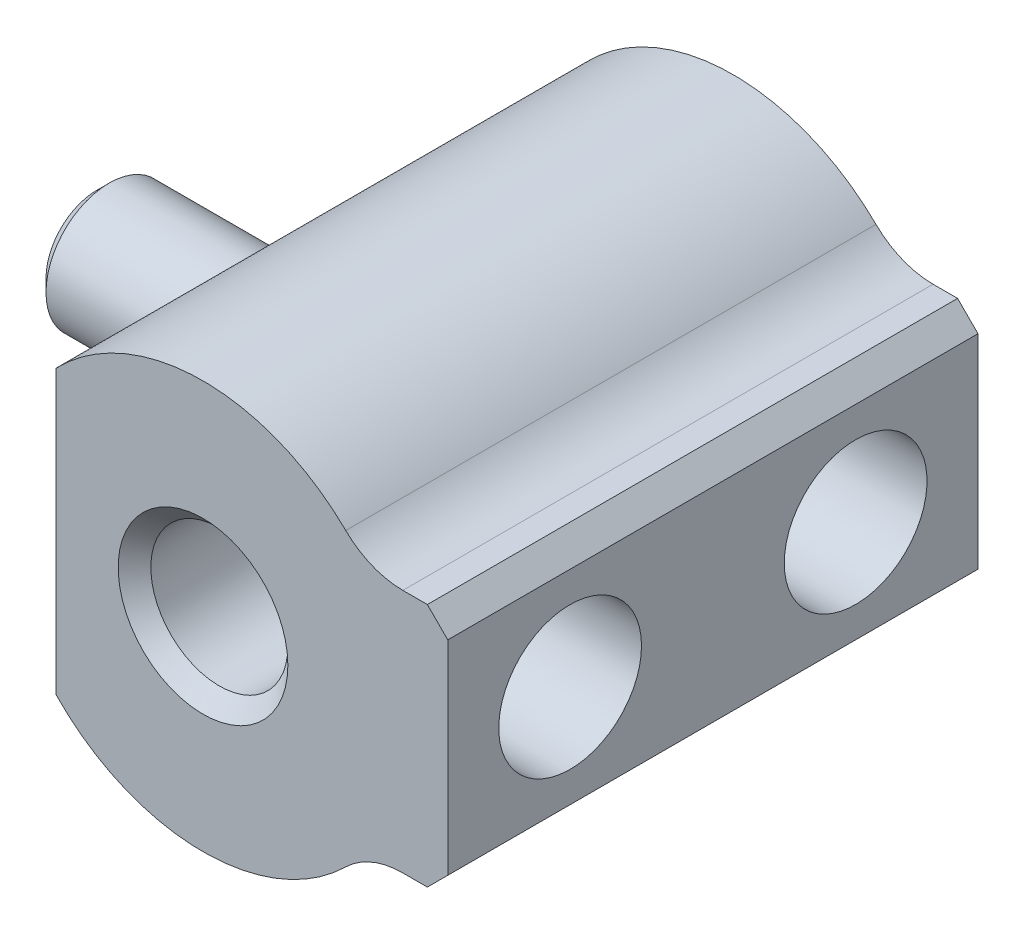
SolidWorks part; units mm, degrees
material "PLA2"
ref_plane "Front Plane" through (0, 0, 0) normal (0, 0, 1) x (1, 0, 0)
ref_plane "Top Plane" through (0, 0, 0) normal (0, 1, 0) x (1, 0, 0)
ref_plane "Right Plane" through (0, 0, 0) normal (1, 0, 0) x (0, 0, -1)
sketch "Sketch1" plane through (0, 0, 0) normal (0, 0, 1) x (1, 0, 0)
  circle A0 centre (0, 0) radius 2.1336
  circle A1 centre (0, 0) radius 6.35
  dimension "D1" = 4.2672
  dimension "D2" = 12.7
extrude "Boss-Extrude1" add sketch "Sketch1" along normal mid plane 16.51
sketch "Sketch3" plane through (0, 0, 8.255) normal (0, 0, 1) x (1, 0, 0)
  line L0 (-4.572, 4.4067) -> (-4.572, -4.4067)
  line L1 (0, 0.0885) -> (0, 50000.0885) construction
  line L3 (5.08, 3.81) -> (5.08, -3.81)
  line L4 (5.08, 0) -> (6.35, 0) construction
  arc A0 (-4.572, 4.4067) -> (-4.572, -4.4067) centre (0, 0) ccw
  arc A2 (5.08, -3.81) -> (5.08, 3.81) centre (0, 0) ccw
  circle A3 centre (0, 0) radius 6.35 construction
  point P1 (-6.35, 0)
  dimension "D1" = 1.778
  dimension "D2" = 1.27
extrude "Cut-Extrude1" cut sketch "Sketch3" against normal through all
sketch "Sketch4" plane through (-4.572, 0, 0) normal (-1, 0, 0) x (0, 0, 1)
  circle A0 centre (0, 0) radius 1.9685
  dimension "D1" = 3.937
extrude "Boss-Extrude2" add sketch "Sketch4" along normal blind 6.985
sketch "Sketch6" plane through (5.08, 0, 0) normal (1, 0, 0) x (0, 0, -1)
  line L4 (-8.255, 3.81) -> (-8.255, -3.81)
  line L5 (-8.255, -3.81) -> (8.255, -3.81)
  line L6 (8.255, -3.81) -> (8.255, 3.81)
  line L7 (8.255, 3.81) -> (-8.255, 3.81)
  line L8 (-8.255, 3.81) -> (-8.255, -3.81)
  line L9 (-8.255, -3.81) -> (8.255, -3.81)
  line L10 (8.255, -3.81) -> (8.255, 3.81)
  line L11 (8.255, 3.81) -> (-8.255, 3.81)
  dimension "D1" = 0
extrude "Boss-Extrude3" add sketch "Sketch6" along normal blind 2.54
fillet "Fillet1" radius 1.27 1 edges at (-4.572, 0, 1.9685)
chamfer "Chamfer1" distance 0.381 angle 45 1 edges at (-11.557, 0, 1.9685)
sketch "Sketch5" plane through (7.62, 0, 0) normal (1, 0, 0) x (0, 0, -1)
  line L0 (0, 0) -> (0, 50000) construction
  line L1 (-4.445, 0) -> (0, 0) construction
  circle A0 centre (-4.445, 0) radius 2.2225
  circle A1 centre (4.445, 0) radius 2.2225
  dimension "D1" = 4.445
  dimension "D2" = 8.89
extrude "Cut-Extrude2" cut sketch "Sketch5" against normal blind 6.35
chamfer "Chamfer2" distance 0.508 angle 45 2 edges at (2.1336, 0, -8.255) (2.1336, 0, 8.255)
fillet "Fillet2" radius 2.54 2 edges at (5.08, -3.81, 0) (5.08, 3.81, 0)
chamfer "Chamfer3" distance 0.635 angle 45 2 edges at (7.62, 3.81, 0) (7.62, -3.81, 0)
